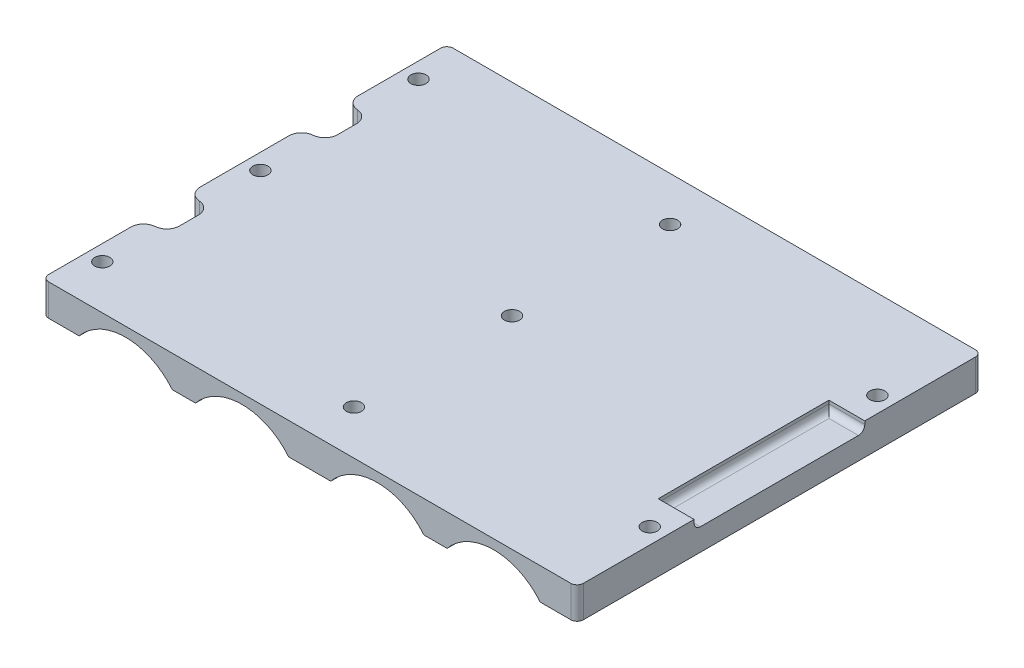
SolidWorks part; units mm, degrees
ref_plane "Front Plane" through (0, 0, 0) normal (0, 0, 1) x (1, 0, 0)
ref_plane "Top Plane" through (0, 0, 0) normal (0, 1, 0) x (1, 0, 0)
ref_plane "Right Plane" through (0, 0, 0) normal (1, 0, 0) x (0, 0, -1)
sketch "Sketch2" plane through (0, 0, 0) normal (0, 0, 1) x (1, 0, 0)
  line L2 (3.3345, -5) -> (-3.3345, -5)
  line L3 (-18.0655, -5) -> (-21.7345, -5)
  line L4 (-36.4655, -5) -> (-42.3, -5)
  line L5 (-42.3, -5) -> (-42.3, 0)
  line L7 (36.4655, -5) -> (42.3, -5)
  line L9 (18.0655, -5) -> (21.7345, -5)
  line L11 (42.3, -5) -> (42.3, 0)
  line L12 (-42.3, 0) -> (42.3, 0)
  line L13 (0, -55) -> (0, 55) construction
  line L14 (25.85, 0) -> (-25.85, 0) construction
  arc A0 (-3.3345, -5) -> (-18.0655, -5) centre (-10.7, -11) ccw
  arc A1 (-21.7345, -5) -> (-36.4655, -5) centre (-29.1, -11) ccw
  arc A2 (21.7345, -5) -> (36.4655, -5) centre (29.1, -11) cw
  arc A3 (3.3345, -5) -> (18.0655, -5) centre (10.7, -11) cw
  point P3 (0, 0)
  dimension "D1" = 9.5
  dimension "D2" = 13.2
  dimension "D3" = 11
  dimension "D4" = 18.4
  dimension "D5" = 18.4
  dimension "D6" = 5
  dimension "D7" = 21.4
extrude "Boss-Extrude1" add sketch "Sketch2" along normal mid plane 64 contours A0 L3 A1 L4 L5 L12 L11 L7 A2 L9 A3 L2
hole_wizard "M2 Clearance Hole1" positions "Sketch7" profile "Sketch8" hole size "M2" standard "ANSI Metric" end condition through all
sketch "Sketch7" plane through (0, -5, 0) normal (0, -1, 0) x (-1, 0, 0)
  line L2 (39.8, 25) -> (0, 25) construction
  line L3 (39.8, 25) -> (39.8, -25) construction
  line L4 (39.8, -25) -> (0, -25) construction
  line L5 (0, 25) -> (0, -25) construction
  line L10 (42.3, -32) -> (42.3, 32) construction
  line L12 (-42.3, -32) -> (-42.3, 32) construction
  line L13 (-36.4655, 32) -> (-42.3, 32) construction
  line L14 (-36.4655, -32) -> (-42.3, -32) construction
  line L15 (0, 2.75) -> (0, -2.75) construction
  point P0 (0, 25)
  point P2 (0, 0)
  point P4 (0, -25)
  point P6 (39.8, -25)
  point P8 (39.8, 0)
  point P10 (39.8, 25)
  point P291 (-39.8, -18)
  point P296 (-39.8, 18)
  dimension "D1" = 2.5
  dimension "D2" = 39.8
  dimension "D3" = 50
  dimension "D5" = 50
  dimension "D6" = 2.5
  dimension "D7" = 2.5
  dimension "D8" = 14
  dimension "D9" = 14
sketch "Sketch8" plane through (0, -5, -25) normal (1, 0, 0) x (0, 0, -1)
  line L0 (0, 0) -> (0, 5)
  line L1 (0, 5) -> (1.2, 5)
  line L2 (1.2, 5) -> (1.2, 0)
  line L5 (1.2, 0) -> (0, 0)
  line L11 (0, -6.35) -> (0, 107.95) construction
  dimension "Thru Hole Dia." = 2.4
  dimension "Thru Hole Depth" = 5
fillet "Fillet1" radius 1 4 edges at (-42.3, -2.5, -32) (42.3, -2.5, -32) (-42.3, -2.5, 32) (42.3, -2.5, 32)
sketch "Sketch9" plane through (0, 0, 0) normal (0, 1, 0) x (1, 0, 0)
  line L0 (42.3, -31) -> (42.3, 31) construction
  line L1 (42.3, -13.5) -> (36.63, -13.5)
  line L2 (42.3, -13.5) -> (42.3, 13.5)
  line L3 (42.3, 13.5) -> (36.63, 13.5)
  line L4 (36.63, -13.5) -> (36.63, 13.5)
  point P6 (42.3, 0)
  point P7 (42.3, 0)
  dimension "D1" = 5.67
  dimension "D2" = 27
extrude "Cut-Extrude1" cut sketch "Sketch9" against normal blind 1.5
fillet "Fillet2" radius 1 3 edges at (39.465, -1.5, -13.5) (36.63, -1.5, 0) (39.465, -1.5, 13.5)
sketch "Sketch11" plane through (0, -5, 0) normal (0, -1, 0) x (1, 0, 0)
  line L0 (2.75, 0) -> (-2.75, 0) construction
  line L1 (-32.3, 19) -> (-42.3, 19)
  line L2 (-32.3, 19) -> (-32.3, 6)
  line L3 (-32.3, 6) -> (-42.3, 6)
  line L4 (-42.3, 19) -> (-42.3, 6)
  line L5 (-32.3, 19) -> (-42.3, 6) construction
  line L6 (-32.3, 6) -> (-42.3, 19) construction
  line L7 (-32.3, -6) -> (-42.3, -6)
  line L8 (-32.3, -6) -> (-32.3, -19)
  line L9 (-32.3, -19) -> (-42.3, -19)
  line L10 (-42.3, -6) -> (-42.3, -19)
  line L11 (-32.3, -6) -> (-42.3, -19) construction
  line L12 (-32.3, -19) -> (-42.3, -6) construction
  line L13 (-42.3, 31) -> (-42.3, -31) construction
  point P0 (-37.3, 12.5)
  point P5 (-37.3, -12.5)
  dimension "D1" = 12.5
  dimension "D2" = 12.5
  dimension "D3" = 13
  dimension "D4" = 13
  dimension "D5" = 10
extrude "Cut-Extrude3" cut sketch "Sketch11" against normal blind 1.5
sketch "Sketch12" plane through (0, -3.5, 0) normal (0, -1, 0) x (1, 0, 0)
  line L0 (-21.7345, 32) -> (-36.4655, 32) construction
  line L4 (-42.3, 16) -> (-42.3, 9)
  line L5 (2.75, 0) -> (-2.75, 0) construction
  line L8 (-40.6, 16) -> (-42.3, 16)
  line L11 (-42.3, 9) -> (-40.6, 9)
  line L12 (-40.6, -9) -> (-42.3, -9)
  line L13 (-42.3, -6) -> (-42.3, -19) construction
  line L14 (-42.3, -9) -> (-42.3, -16)
  line L15 (-42.3, -16) -> (-40.6, -16)
  line L16 (-38.6, 14) -> (-38.6, 11)
  line L17 (-38.6, -11) -> (-38.6, -14)
  line L18 (-42.3, 19) -> (-42.3, 6) construction
  arc A4 (-40.6, 16) -> (-38.6, 14) centre (-40.6, 14) cw
  arc A5 (-38.6, 11) -> (-40.6, 9) centre (-40.6, 11) cw
  arc A6 (-40.6, -9) -> (-38.6, -11) centre (-40.6, -11) cw
  arc A7 (-38.6, -14) -> (-40.6, -16) centre (-40.6, -14) cw
  point P3 (-29.1, 32)
  point P4 (-41.45, 16)
  dimension "D5" = 9
  dimension "D6" = 2
  dimension "D7" = 2
  dimension "D1" = 9.5
  dimension "D2" = 7
  dimension "D3" = 7
  dimension "D4" = 18
extrude "Cut-Extrude4" cut sketch "Sketch12" against normal through all
fillet "Fillet4" radius 2 4 edges at (-42.3, -1.75, -16) (-42.3, -1.75, -9) (-42.3, -1.75, 9) (-42.3, -1.75, 16)
